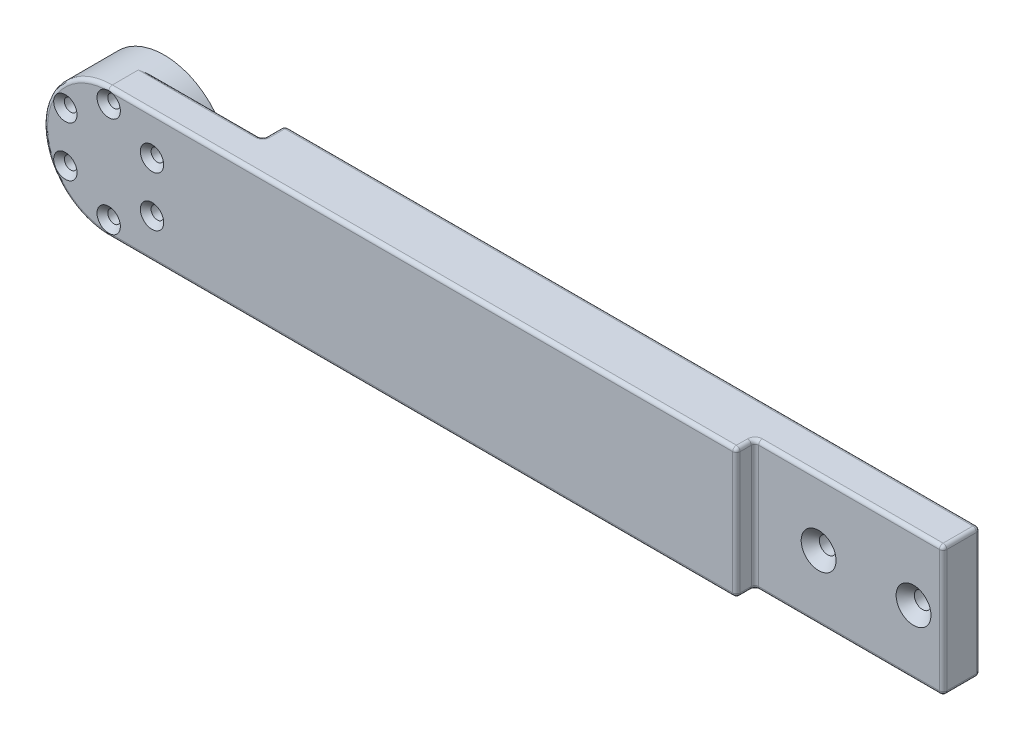
SolidWorks part; units mm, degrees
material "ABS"
ref_plane "Front Plane" through (0, 0, 0) normal (0, 0, 1) x (1, 0, 0)
ref_plane "Top Plane" through (0, 0, 0) normal (0, 1, 0) x (1, 0, 0)
ref_plane "Right Plane" through (0, 0, 0) normal (1, 0, 0) x (0, 0, -1)
sketch "Sketch1" plane through (0, 0, 0) normal (0, 0, 1) x (1, 0, 0)
  line L0 (-260.6645, 0.2452) -> (-60.6645, 0.2452)
  line L2 (-60.6645, -34.7548) -> (-260.6645, -34.7548)
  line L3 (-60.6645, 0.2452) -> (-40.5345, 0.2452)
  line L4 (-40.5345, 0.2452) -> (-40.5345, -34.7548)
  line L5 (-40.5345, -34.7548) -> (-60.6645, -34.7548)
  arc A1 (-260.6645, -34.7548) -> (-260.6645, 0.2452) centre (-260.6645, -17.2548) cw
  dimension "D1" = 200
  dimension "D2" = 200
  dimension "D3" = 17.5
extrude "Boss-Extrude1" add sketch "Sketch1" along normal blind 15
sketch "Sketch3" plane through (0, 0, 15) normal (0, 0, 1) x (1, 0, 0)
  line L0 (-260.6645, -17.2548) -> (-260.6645, 23.4981)
  line L1 (-212.9979, 0.2452) -> (-212.9979, -34.7548)
  line L2 (-260.6645, -17.2548) -> (-245.509, -8.5048)
  line L3 (-260.6645, -17.2548) -> (-304.6929, 8.1651)
  line L4 (-260.6645, -17.2548) -> (-302.1274, -41.1934)
  line L5 (-260.6645, -17.2548) -> (-245.509, -26.0048)
  line L6 (-260.6645, -17.2548) -> (-260.6645, -59.9525)
  line L7 (-260.6645, 0.2452) -> (-212.9979, 0.2452)
  line L8 (-40.5345, 0.2452) -> (-260.6645, 0.2452) construction
  line L9 (-260.6645, -34.7548) -> (-40.5345, -34.7548) construction
  line L10 (-212.9979, -34.7548) -> (-260.6645, -34.7548)
  circle A0 centre (-260.6645, -17.2548) radius 17.5
  circle A1 centre (-260.6645, -17.2548) radius 13.5
  arc A2 (-260.6645, 0.2452) -> (-260.6645, -34.7548) centre (-260.6645, -17.2548) cw
  arc A3 (-260.6645, -34.7548) -> (-260.6645, 0.2452) centre (-260.6645, -17.2548) ccw
  dimension "D1" = 60
  dimension "D5" = 27
  dimension "D6" = 35
  dimension "D2" = 60
  dimension "D3" = 60
  dimension "D4" = 60
  dimension "D7" = 47.6666
hole_wizard "CSK for M3 Countersunk Flat Head Screw1" positions "3DSketch5" profile "Sketch7" countersink size "M3" standard "ISO" end condition through all
sketch3d "3DSketch5"
  line L0 (-260.6645, -17.2548, 15) -> (-260.6645, 23.4981, 15) construction
  line L1 (-260.6645, -17.2548, 15) -> (-304.6929, 8.1651, 15) construction
  line L2 (-260.6645, -17.2548, 15) -> (-302.1274, -41.1934, 15) construction
  line L3 (-260.6645, -17.2548, 15) -> (-260.6645, -59.9525, 15) construction
  line L4 (-260.6645, -17.2548, 15) -> (-245.509, -26.0048, 15) construction
  line L5 (-260.6645, -17.2548, 15) -> (-245.509, -8.5048, 15) construction
  circle A0 centre (-260.6645, -17.2548, 15) radius 13.5 construction
  point P0 (-260.6645, -3.7548, 15)
  point P6 (-260.6645, -17.2548, 28.5)
  point P7 (-272.3558, -10.5048, 15)
  point P11 (-272.3558, -24.0048, 15)
  point P15 (-260.6645, -30.7548, 15)
  point P19 (-248.9731, -24.0048, 15)
  point P23 (-248.9731, -10.5048, 15)
sketch "Sketch7" plane through (-260.6645, -3.7548, 15) normal (1, 0, 0) x (0, -1, 0)
  line L0 (0, 0) -> (0, 15)
  line L1 (0, 15) -> (1.7, 15)
  line L2 (1.7, 15) -> (1.7, 1.45)
  line L3 (1.7, 1.45) -> (3.15, 0)
  line L5 (3.15, 0) -> (0, 0)
  line L6 (-1.7, 1.45) -> (-3.15, 0) construction
  line L11 (0, -6.35) -> (0, 107.95) construction
  dimension "Thru Hole Dia." = 3.4
  dimension "Thru Hole Depth" = 15
  dimension "Near C'Sink Dia." = 6.3
  dimension "Near C'Sink Angle" = 90
sketch "Sketch13" plane through (0, 0, 15) normal (0, 0, 1) x (1, 0, 0)
  line L0 (-40.5345, 0.2452) -> (-91.2984, 0.2452)
  line L1 (-40.5345, 0.2452) -> (-212.9979, 0.2452) construction
  line L2 (-91.2984, 0.2452) -> (-91.2984, -34.7548)
  line L3 (-212.9979, -34.7548) -> (-40.5345, -34.7548) construction
  line L4 (-91.2984, -34.7548) -> (-40.5345, -34.7548)
  line L5 (-40.5345, -34.7548) -> (-40.5345, 0.2452)
  dimension "D1" = 50.764
extrude "Cut-Extrude2" cut sketch "Sketch13" against normal blind 5
fillet "Fillet4" radius 1 1 edges at (-40.5345, -17.2548, 10)
fillet "Fillet5" radius 1 1 edges at (-40.5345, -17.2548, 0)
sketch "Sketch15" plane through (0, 0, 0) normal (0, 0, -1) x (-1, 0, 0)
  line L0 (260.6645, -34.7548) -> (41.5345, -34.7548) construction
  line L2 (260.6645, 0.2452) -> (228.1455, 0.2452)
  line L3 (41.5345, 0.2452) -> (260.6645, 0.2452) construction
  line L4 (228.1455, 0.2452) -> (228.1455, -34.7548)
  line L5 (228.1455, -34.7548) -> (260.6645, -34.7548)
  arc A2 (260.6645, 0.2452) -> (260.6645, -34.7548) centre (260.6645, -17.2548) ccw
extrude "Cut-Extrude4" cut sketch "Sketch15" against normal blind 6
fillet "Fillet9" radius 1 1 edges at (-91.2984, -17.2548, 10)
fillet "Fillet10" radius 1 1 edges at (-91.2984, -17.2548, 15)
fillet "Fillet11" radius 1 19 edges at (-134.84, 0.2452, 0) (-40.8274, 0.2452, 0.2929) (-40.5345, 0.2452, 5) (-40.8274, 0.2452, 9.7071) (-65.9164, 0.2452, 10) (-91.0055, 0.2452, 10.2929) (-91.2984, 0.2452, 12.5) (-91.5913, 0.2452, 14.7071) (-176.4814, 0.2452, 15) (-278.1645, -17.2548, 15) (-176.4814, -34.7548, 15) (-91.5913, -34.7548, 14.7071) (-91.2984, -34.7548, 12.5) (-91.0055, -34.7548, 10.2929) (-134.84, -34.7548, 0) (-40.8274, -34.7548, 0.2929) (-40.5345, -34.7548, 5) (-40.8274, -34.7548, 9.7071) (-65.9164, -34.7548, 10)
fillet "Fillet12" radius 1 1 edges at (-228.1455, -17.2548, 6)
fillet "Fillet13" radius 1 9 edges at (-244.905, 0.2452, 6) (-228.4384, 0.2452, 5.7071) (-228.1455, 0.2452, 3) (-228.1455, -0.0476, 0.2929) (-244.905, -34.7548, 6) (-228.4384, -34.7548, 5.7071) (-228.1455, -34.7548, 3) (-228.1455, -34.4619, 0.2929) (-228.1455, -17.2548, 0)
sketch "Sketch17" plane through (0, 0, 10) normal (0, 0, 1) x (1, 0, 0)
  line L0 (-41.5345, -17.2548) -> (-49.1224, -17.2548)
  line L1 (-41.5345, -33.7548) -> (-41.5345, -0.7548) construction
  line L2 (-49.1224, -17.2548) -> (-74.1224, -17.2548)
  line L3 (-74.1224, -17.2548) -> (-74.1224, -22.364)
  line L4 (-74.1224, -22.364) -> (-41.5345, -22.364)
  line L5 (-41.5345, -22.364) -> (-41.5345, -17.2548)
  dimension "D1" = 25
hole_wizard "CSK for M4 Countersunk Flat Head Screw1" positions "3DSketch6" profile "Sketch18" countersink size "M4" standard "ISO" end condition through all
sketch3d "3DSketch6"
  line L0 (-41.5345, -17.2548, 10) -> (-49.1224, -17.2548, 10) construction
  point P0 (-74.1224, -17.2548, 10)
  point P3 (-48.5119, -17.2548, 10)
sketch "Sketch18" plane through (-74.1224, -17.2548, 10) normal (1, 0, 0) x (0, -1, 0)
  line L0 (0, 0) -> (0, 10)
  line L1 (0, 10) -> (2.25, 10)
  line L2 (2.25, 10) -> (2.25, 2.45)
  line L3 (2.25, 2.45) -> (4.7, 0)
  line L5 (4.7, 0) -> (0, 0)
  line L6 (-2.25, 2.45) -> (-4.7, 0) construction
  line L11 (0, -6.35) -> (0, 107.95) construction
  dimension "Thru Hole Dia." = 4.5
  dimension "Thru Hole Depth" = 10
  dimension "Near C'Sink Dia." = 9.4
  dimension "Near C'Sink Angle" = 90
